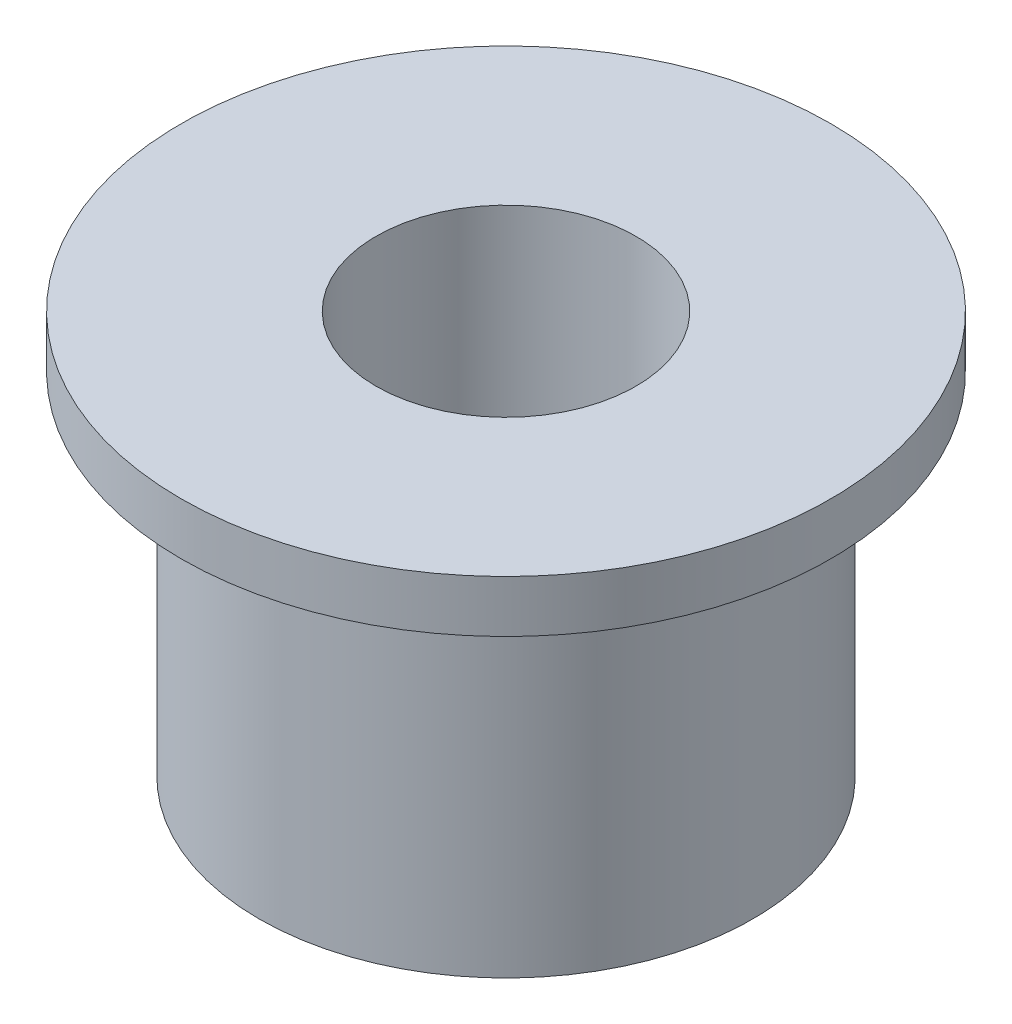
SolidWorks part; units mm, degrees
material "Plain Carbon Steel"
ref_plane "Front Plane" through (0, 0, 0) normal (0, 0, 1) x (1, 0, 0)
ref_plane "Top Plane" through (0, 0, 0) normal (0, 1, 0) x (1, 0, 0)
ref_plane "Right Plane" through (0, 0, 0) normal (1, 0, 0) x (0, 0, -1)
sketch "Sketch2" plane through (0, 0, 0) normal (0, 1, 0) x (1, 0, 0)
  circle A0 centre (0, 0) radius 25
  circle A1 centre (0, 0) radius 10
  circle A2 centre (0, 0) radius 19
  dimension "D1" = 50
  dimension "D2" = 38
  dimension "D3" = 20
extrude "Boss-Extrude1" add sketch "Sketch2" against normal blind 4 contours A0 A2 region at (-24.2929, 0, 0)
extrude "Boss-Extrude2" add sketch "Sketch2<3>" against normal blind 31 contours A2 A1 region at (-18.4626, 0, 0)
sketch "Sketch2<3>" plane through (0, 0, 0) normal (0, 1, 0) x (1, 0, 0) same geometry as "Sketch2"
